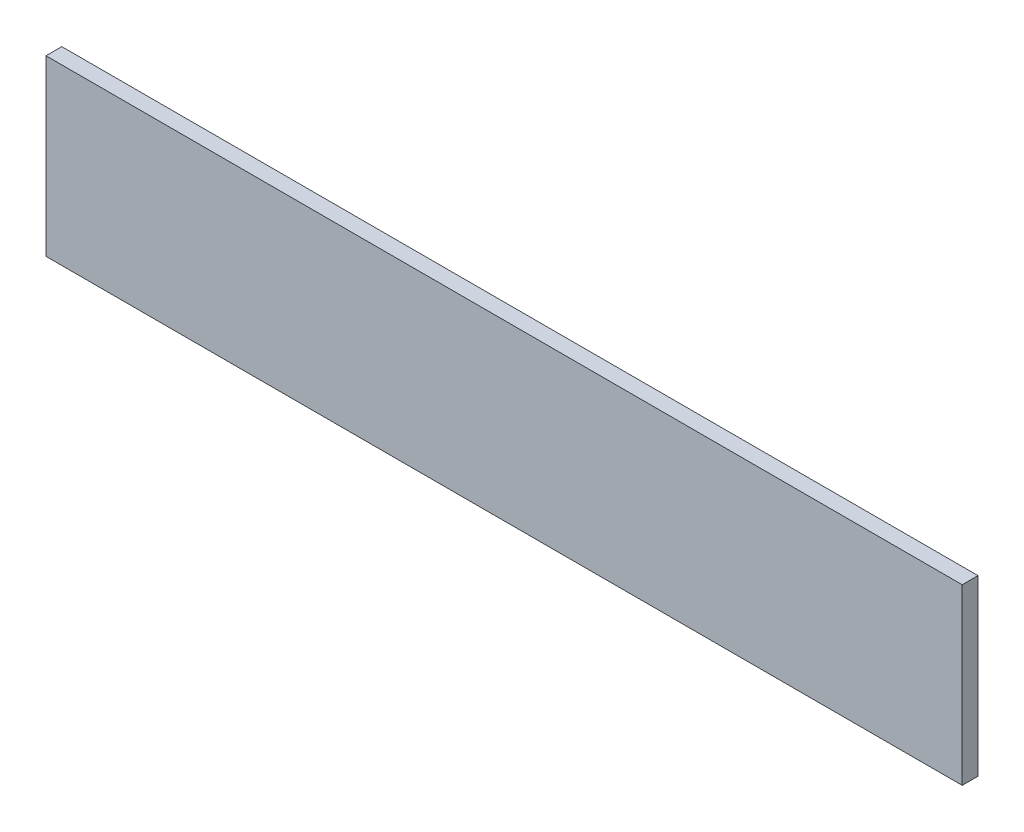
SolidWorks part; units mm, degrees
ref_plane "Plan de face" through (0, 0, 0) normal (0, 0, 1) x (1, 0, 0)
ref_plane "Plan de dessus" through (0, 0, 0) normal (0, 1, 0) x (1, 0, 0)
ref_plane "Plan de droite" through (0, 0, 0) normal (1, 0, 0) x (0, 0, -1)
sketch "Esquisse1" plane through (0, 0, 0) normal (0, 0, 1) x (1, 0, 0)
  line L1 (0, 0) -> (580, 0)
  line L2 (0, 0) -> (0, 110)
  line L3 (0, 110) -> (580, 110)
  line L4 (580, 0) -> (580, 110)
  dimension "D1" = 580
  dimension "D2" = 110
extrude "Boss.-Extru.1" add sketch "Esquisse1" along normal blind 10
